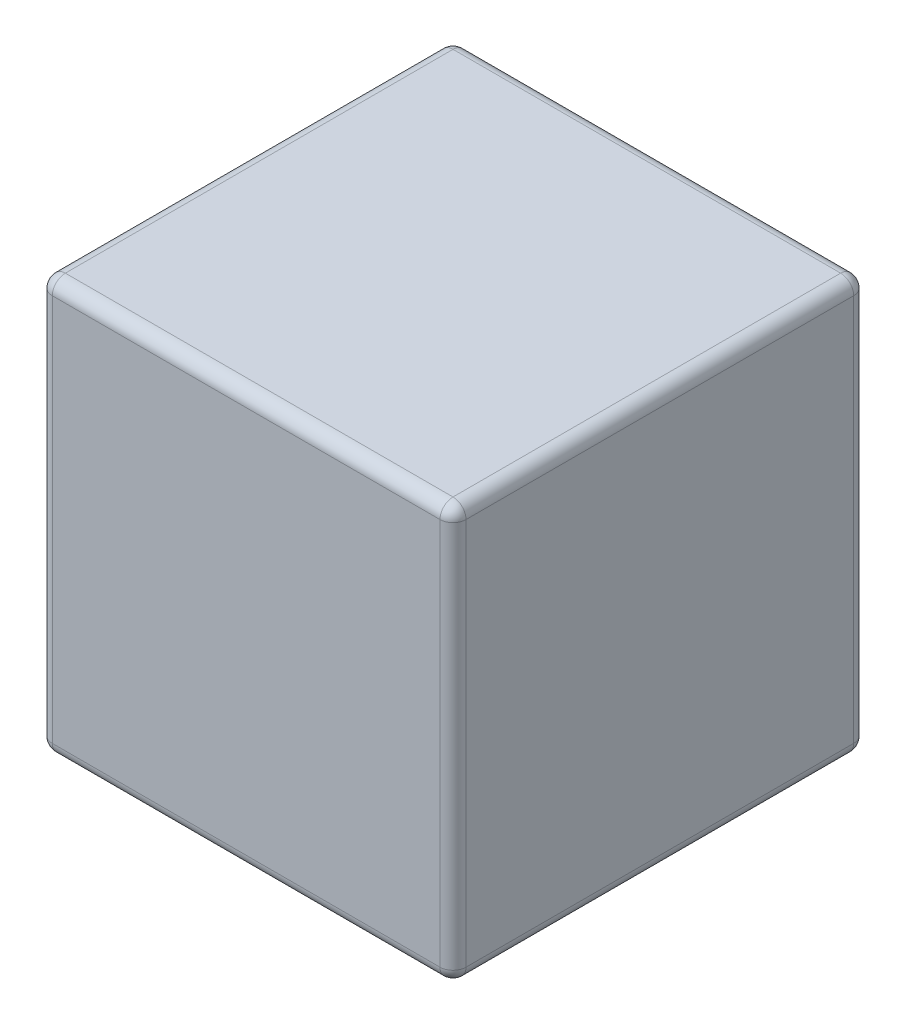
SolidWorks part; units mm, degrees
material "Nickel"
ref_plane "Front Plane" through (0, 0, 0) normal (0, 0, 1) x (1, 0, 0)
ref_plane "Top Plane" through (0, 0, 0) normal (0, 1, 0) x (1, 0, 0)
ref_plane "Right Plane" through (0, 0, 0) normal (1, 0, 0) x (0, 0, -1)
sketch "Sketch1" plane through (0, 0, 0) normal (0, 1, 0) x (1, 0, 0)
  line L1 (-1.5875, 1.5875) -> (1.5875, 1.5875)
  line L2 (-1.5875, 1.5875) -> (-1.5875, -1.5875)
  line L3 (-1.5875, -1.5875) -> (1.5875, -1.5875)
  line L4 (1.5875, 1.5875) -> (1.5875, -1.5875)
  line L5 (-1.5875, 1.5875) -> (1.5875, -1.5875) construction
  line L6 (-1.5875, -1.5875) -> (1.5875, 1.5875) construction
  point P0 (0, 0)
  dimension "D1" = 3.175
  dimension "D2" = 3.175
extrude "Boss-Extrude1" add sketch "Sketch1" along normal blind 3.175
fillet "Fillet1" radius 0.1 12 edges at (0, 3.175, 1.5875) (1.5875, 1.5875, -1.5875) (-1.5875, 1.5875, -1.5875) (-1.5875, 1.5875, 1.5875) (1.5875, 1.5875, 1.5875) (-1.5875, 3.175, 0) (0, 3.175, -1.5875) (1.5875, 3.175, 0) (0, 0, 1.5875) (-1.5875, 0, 0) (0, 0, -1.5875) (1.5875, 0, 0)
